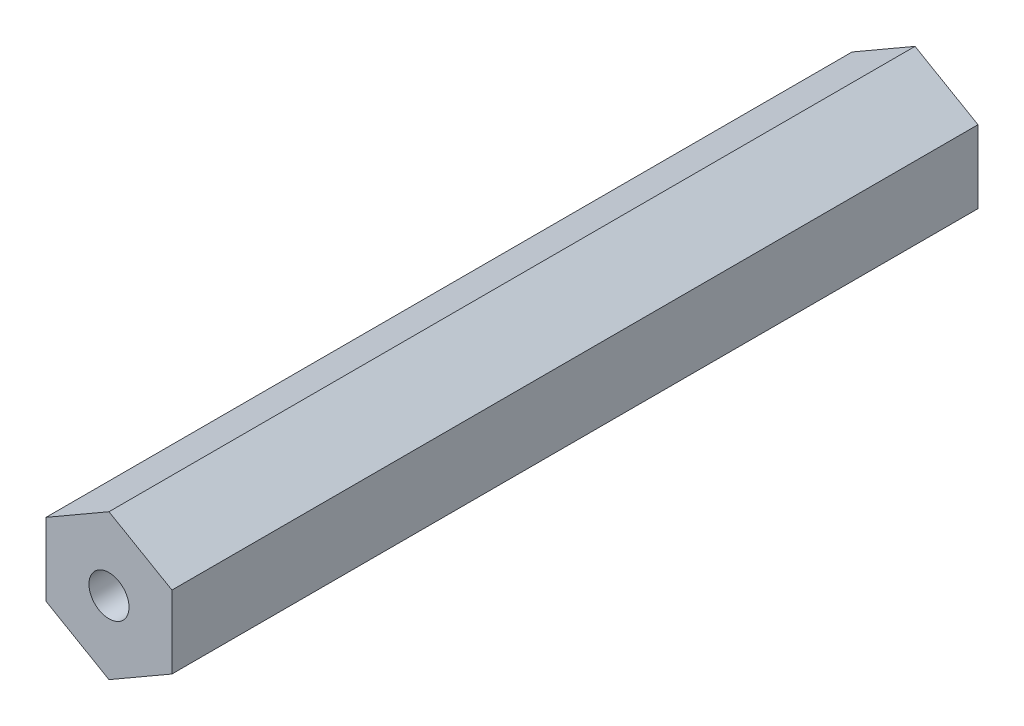
SolidWorks part; units mm, degrees
other "Markup1"
sketch "Sketch3" plane through (6.35, 7.3323, -19.05) normal (0.3384, 0.0641, -0.9388) x (-0.9259, -0.1556, -0.3443)
material "7075-T6 (SN)"
ref_plane "Front Plane" through (0, 0, 0) normal (0, 0, 1) x (1, 0, 0)
ref_plane "Top Plane" through (0, 0, 0) normal (0, 1, 0) x (1, 0, 0)
ref_plane "Right Plane" through (0, 0, 0) normal (1, 0, 0) x (0, 0, -1)
sketch "Sketch1" plane through (0, 0, 0) normal (0, 0, 1) x (1, 0, 0)
  line L1 (0, 7.3323) -> (-6.35, 3.6662)
  line L2 (-6.35, 3.6662) -> (-6.35, -3.6662)
  line L3 (-6.35, -3.6662) -> (0, -7.3323)
  line L4 (0, -7.3323) -> (6.35, -3.6662)
  line L5 (6.35, -3.6662) -> (6.35, 3.6662)
  line L6 (6.35, 3.6662) -> (0, 7.3323)
  circle A0 centre (0, 0) radius 6.35 construction
  dimension "D1" = 12.7
extrude "Boss-Extrude1" add sketch "Sketch1" along normal mid plane 81.28
sketch "Sketch2" plane through (0, 0, -40.64) normal (0, 0, -1) x (-1, 0, 0)
  circle A0 centre (0, 0) radius 2.0193
  point P3 (0, 0)
  dimension "D1" = 4.0386
sketch "Sketch4" plane through (0, 0, -40.64) normal (0, 0, -1) x (-1, 0, 0)
  point P0 (0, 0)
hole_wizard "#10-32 Tapped Hole1" positions "Sketch4" profile "Sketch5" tap size "#10-32" standard "ANSI Inch"
sketch "Sketch5" plane through (0, 0, -40.64) normal (1, 0, 0) x (0, 1, 0)
  line L0 (0, 0) -> (0, 13.1513)
  line L1 (0, 13.1513) -> (2.0193, 11.938)
  line L2 (2.0193, 11.938) -> (2.0193, 0)
  line L5 (2.0193, 0) -> (0, 0)
  line L10 (0, 13.1513) -> (-2.0193, 11.938) construction
  line L11 (0, -6.35) -> (0, 107.95) construction
  dimension "Tap Drill Dia." = 4.0386
  dimension "Tap Drill Depth" = 11.938
  dimension "Drill Angle" = 118
cosmetic thread "Hole Thread1" parameters "D1"=9.652, "D2"=4.826
mirror "Mirror1" about plane through (0, 0, 0) normal (0, 0, 1) of "#10-32 Tapped Hole1"
cosmetic thread "Hole Thread2" parameters "D1"=9.652, "D2"=4.826
